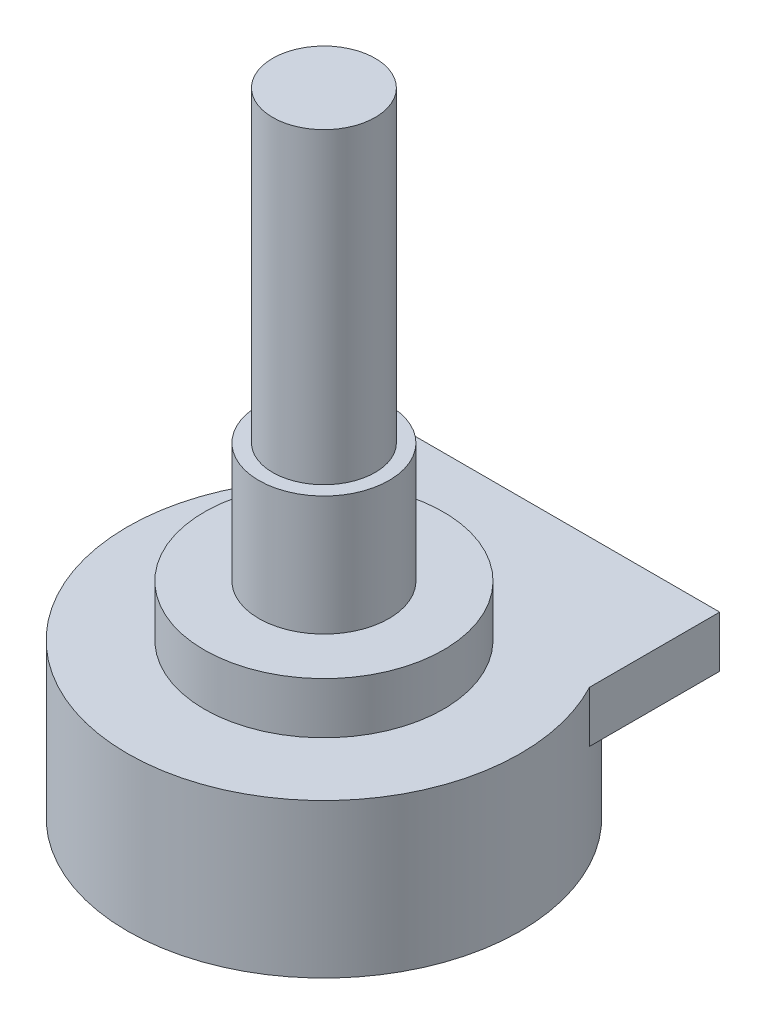
SolidWorks part; units mm, degrees
ref_plane "Front Plane" through (0, 0, 0) normal (0, 0, 1) x (1, 0, 0)
ref_plane "Top Plane" through (0, 0, 0) normal (0, 1, 0) x (1, 0, 0)
ref_plane "Right Plane" through (0, 0, 0) normal (1, 0, 0) x (0, 0, -1)
sketch "Sketch1" plane through (0, 0, 0) normal (0, 1, 0) x (1, 0, 0)
  line L0 (1.1176, 8.7884) -> (1.1176, -34.6964) construction
  line L1 (-9.0424, 8.7884) -> (11.2776, 8.7884)
  line L2 (-9.0424, 8.7884) -> (-9.0424, 1.1684)
  line L4 (11.2776, 8.7884) -> (11.2776, 1.1684)
  arc A0 (-9.0424, 1.1684) -> (11.2776, 1.1684) centre (1.1176, -4.219) ccw
  circle A1 centre (1.1176, -4.219) radius 3.81
  circle A2 centre (1.1176, -4.219) radius 3
  circle A3 centre (1.1176, -4.219) radius 7
  dimension "D1" = 20.32
  dimension "D2" = 7.62
extrude "Boss-Extrude1" add sketch "Sketch1" along normal blind 9 contours L0 L1 L2 A0 A3 | L1 L0 A3 A0 L4 region at (6.1976, 0, -8.5177) region at (0.8469, 0, -5.7847)
extrude "Boss-Extrude2" add sketch "Sketch1<3>" along normal blind 12 contours L0 A3 A1 | A3 L0 A1 region at (5.9567, 0, -0.62) region at (0.9611, 0, -1.186)
sketch "Sketch1<3>" plane through (0, 0, 0) normal (0, 1, 0) x (1, 0, 0) same geometry as "Sketch1"
extrude "Boss-Extrude3" add sketch "Sketch1<4>" along normal blind 19 contours L0 A1 A2 | A1 L0 A2 region at (3.7514, 0, 1.5852) region at (1.0324, 0, 0.814)
sketch "Sketch1<4>" plane through (0, 0, 0) normal (0, 1, 0) x (1, 0, 0) same geometry as "Sketch1"
extrude "Boss-Extrude4" add sketch "Sketch1<5>" along normal blind 37 contours L0 A2 | A2 L0 region at (2.3908, 0, 4.219) region at (-0.1556, 0, 4.219)
sketch "Sketch1<5>" plane through (0, 0, 0) normal (0, 1, 0) x (1, 0, 0) same geometry as "Sketch1"
sketch "Sketch2" plane through (0, 0, 0) normal (0, -1, 0) x (-1, 0, 0)
  line L0 (-1.1176, -15.719) -> (-1.1176, 8.7884) construction
  line L1 (9.0424, 8.7884) -> (-11.2776, 8.7884) construction
  line L2 (10.3824, -4.219) -> (-12.6176, -4.219) construction
  line L3 (-11.2776, 8.7884) -> (-11.2776, 1.1684) construction
  line L4 (9.0424, 1.1684) -> (9.0424, 8.7884)
  line L5 (9.0424, 8.7884) -> (-11.2776, 8.7884)
  line L6 (-11.2776, 8.7884) -> (-11.2776, 1.1684)
  arc A0 (-11.2776, 1.1684) -> (9.0424, 1.1684) centre (-1.1176, -4.219) ccw construction
  arc A1 (9.0424, 1.1684) -> (-11.2776, 1.1684) centre (-1.1176, -4.219) ccw
extrude "Cut-Extrude1" cut sketch "Sketch2" against normal blind 6
